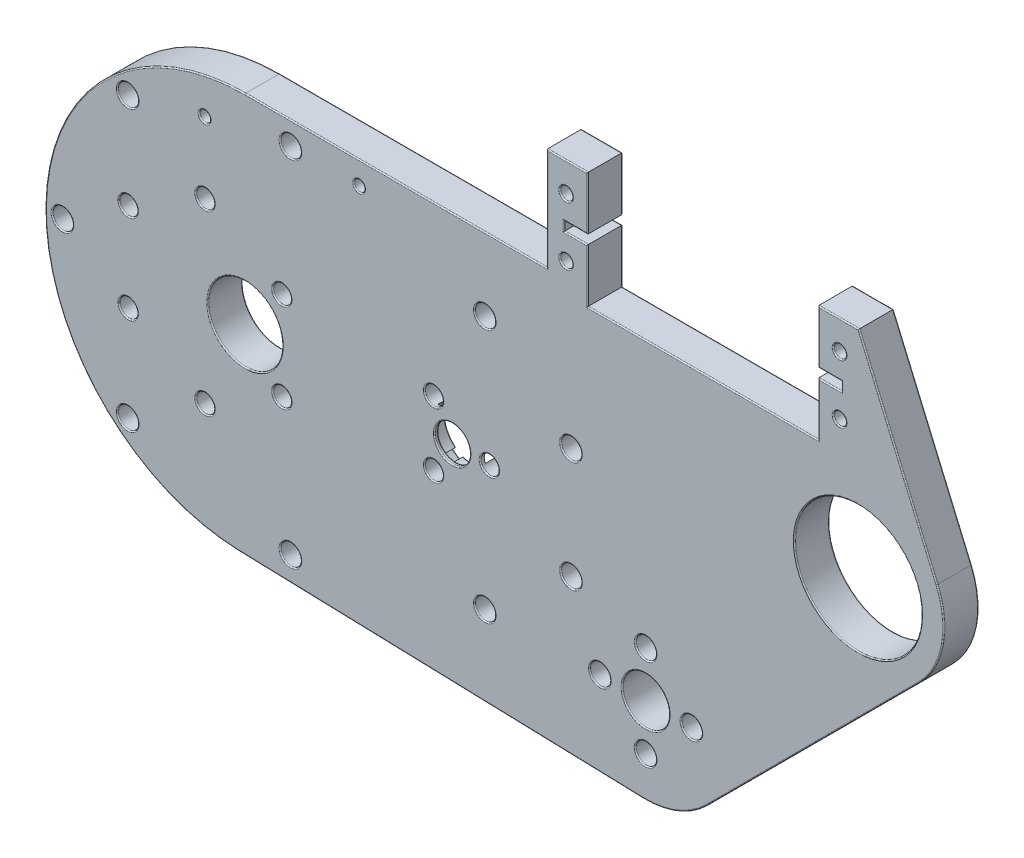
SolidWorks part; units mm, degrees
ref_plane "정면" through (0, 0, 0) normal (0, 0, 1) x (1, 0, 0)
ref_plane "윗면" through (0, 0, 0) normal (0, 1, 0) x (1, 0, 0)
ref_plane "우측면" through (0, 0, 0) normal (1, 0, 0) x (0, 0, -1)
sketch "스케치1" plane through (0, 0, 0) normal (0, 0, 1) x (1, 0, 0)
  line L0 (0, 0) -> (-51.1815, 0) construction
  line L1 (0, 0) -> (0, -16.6153) construction
  line L2 (-29.1144, 27.6051) -> (4.8481, 18.8877)
  line L7 (-29.1144, -27.6051) -> (4.8481, -18.8877)
  line L8 (-29.0149, 27.9926) -> (4.9475, 19.2752)
  line L9 (-29.0149, -27.9926) -> (4.9475, -19.2752)
  line L10 (-27.5232, 33.8042) -> (6.4392, 25.0868)
  line L11 (-27.5232, -33.8042) -> (6.4392, -25.0868)
  circle A3 centre (-43.2, 0) radius 15.5 construction
  circle A4 centre (-36.2, 0) radius 6.5
  circle A5 centre (-43.2, -15.5) radius 1.6
  circle A6 centre (-56.6234, -7.75) radius 1.6
  circle A7 centre (-56.6234, 7.75) radius 1.6
  circle A8 centre (-43.2, 15.5) radius 1.6
  circle A9 centre (-29.7766, 7.75) radius 1.6
  circle A10 centre (-29.7766, -7.75) radius 1.6
  circle A11 centre (0, 0) radius 5.15
  arc A12 (-29.1144, 27.6051) -> (-29.1144, -27.6051) centre (-36.2, 0) ccw
  arc A13 (4.8481, -18.8877) -> (4.8481, 18.8877) centre (0, 0) ccw
  arc A14 (4.9475, -19.2752) -> (4.9475, 19.2752) centre (0, 0) ccw
  arc A15 (-29.0149, 27.9926) -> (-29.0149, -27.9926) centre (-36.2, 0) ccw
  arc A16 (6.4392, -25.0868) -> (6.4392, 25.0868) centre (0, 0) ccw
  arc A17 (-27.5232, 33.8042) -> (-27.5232, -33.8042) centre (-36.2, 0) ccw
  circle A18 centre (0, 0) radius 6.5 construction
  circle A19 centre (6.5, 0) radius 1.6
  circle A20 centre (0, 0) radius 6.5 construction
  circle A21 centre (-3.25, -5.6292) radius 1.6
  circle A22 centre (0, 0) radius 6.5 construction
  circle A23 centre (-3.25, 5.6292) radius 1.6
  point P12 (0, 0)
  point P30 (-43.2, 0)
  point P51 (0, 0)
  dimension "D6" = 31
  dimension "D7" = 13
  dimension "D9" = 3.2
  dimension "D12" = 10.3
  dimension "D13" = 0.4
  dimension "D14" = 57
  dimension "D18" = 39
  dimension "D16" = 13
  dimension "D2" = 3.2
  dimension "D8" = 7
  dimension "D11" = 36.2
  dimension "D15" = 6
  dimension "D10" = 6
  dimension "D3" = 3
extrude "보스-돌출1" add sketch "스케치1" along normal blind 8 contours A23 A11 A21 A19 | L7 A13 L2 A12 A23 A11 A19 A21 A4 A5 A6 A7 A8 A9 A10 | L8 A15 L9 A14 A13 L7 A12 L2 region at (-24.9126, 0, 0) region at (-12.0593, 23.5343, 0) region at (0, 0, 0)
sketch "스케치2" plane through (0, 0, 0) normal (0, 0, -1) x (-1, 0, 0)
  circle A0 centre (0, 0) radius 9
  dimension "D1" = 18
extrude "컷-돌출1" cut sketch "스케치2" against normal blind 3
extrude "보스-돌출2" add sketch "스케치1<3>" along normal blind 29.8 contours L10 A17 L11 A16 A15 L8 A14 L9 region at (-10.8391, 28.288, 0)
sketch "스케치1<3>" plane through (0, 0, 0) normal (0, 0, 1) x (1, 0, 0) same geometry as "스케치1"
sketch "스케치3" plane through (0, 0, 0) normal (0, 0, -1) x (-1, 0, 0)
  line L2 (-33.3521, -36.9933) -> (37.2421, -34.8844)
  line L3 (-71.5915, 30.105) -> (34.6377, 34.865)
  line L4 (-81.5266, 4.5134) -> (-44.4066, -32.6066)
  line L5 (27.5232, 33.8042) -> (-6.4392, 25.0868)
  line L6 (-6.4392, -25.0868) -> (27.5232, -33.8042)
  line L7 (27.5232, 33.8042) -> (-6.4392, 25.0868)
  line L8 (-6.4392, -25.0868) -> (27.5232, -33.8042)
  circle A0 centre (-70.92, 15.12) radius 11.1
  circle A1 centre (-33.8, -22) radius 4.1
  circle A2 centre (36.2, 0) radius 6.5 construction
  arc A3 (-71.5915, 30.105) -> (-81.5266, 4.5134) centre (-70.92, 15.12) ccw
  arc A4 (-44.4066, -32.6066) -> (-33.3521, -36.9933) centre (-33.8, -22) ccw
  arc A5 (27.5232, -33.8042) -> (27.5232, 33.8042) centre (36.2, 0) ccw construction
  arc A7 (-6.4392, 25.0868) -> (-6.4392, -25.0868) centre (0, 0) ccw
  arc A8 (27.5232, -33.8042) -> (27.5232, 33.8042) centre (36.2, 0) ccw
  arc A9 (-6.4392, 25.0868) -> (-6.4392, -25.0868) centre (0, 0) ccw
  arc A10 (27.5232, -33.8042) -> (27.5232, 33.8042) centre (36.2, 0) ccw
  circle A14 centre (-33.8, -14) radius 1.8
  circle A15 centre (-25.8, -22) radius 1.8
  circle A16 centre (-33.8, -30) radius 1.8
  circle A17 centre (-41.8, -22) radius 1.8
  point P32 (-70.92, 15.12)
  point P41 (-33.8, -22)
  line M18 (27.5232, 33.8042) -> (-6.4392, 25.0868)
  arc M19 (-6.4392, 25.0868) -> (-6.4392, -25.0868) centre (0, 0) ccw
  line M20 (-6.4392, -25.0868) -> (27.5232, -33.8042)
  arc M21 (27.5232, -33.8042) -> (27.5232, 33.8042) centre (36.2, 0) ccw
  dimension "D1" = 22.2
  dimension "D2" = 8.2
  dimension "D3" = 70
  dimension "D7" = 30
  dimension "D12" = 3.6
  dimension "D4" = 22
  dimension "D5" = 37.12
  dimension "D6" = 37.12
  dimension "D13" = 8
  dimension "D8" = 0
  dimension "D14" = 4
extrude "보스-돌출3" add sketch "스케치3" against normal blind 5.55 contours L4 A4 L2 L3 A3 A0 A1 M21 M20 M19 M18 region at (36.4383, 0.1602, 0)
sketch "스케치5" plane through (0, 0, 0) normal (0, 0, -1) x (-1, 0, 0)
  line L3 (-33.3521, -36.9933) -> (37.2421, -34.8844)
  line L4 (34.6377, 34.865) -> (-71.5915, 30.105)
  line L5 (-81.5266, 4.5134) -> (-44.4066, -32.6066)
  line L6 (-33.3521, -36.9933) -> (37.2421, -34.8844)
  line L7 (34.6377, 34.865) -> (-71.5915, 30.105)
  line L8 (-81.5266, 4.5134) -> (-44.4066, -32.6066)
  arc A3 (-44.4066, -32.6066) -> (-33.3521, -36.9933) centre (-33.8, -22) ccw
  arc A4 (37.2421, -34.8844) -> (34.6377, 34.865) centre (36.2, 0) ccw
  arc A5 (-71.5915, 30.105) -> (-81.5266, 4.5134) centre (-70.92, 15.12) ccw
  arc A6 (-44.4066, -32.6066) -> (-33.3521, -36.9933) centre (-33.8, -22) ccw
  arc A7 (37.2421, -34.8844) -> (34.6377, 34.865) centre (36.2, 0) ccw
  arc A8 (-71.5915, 30.105) -> (-81.5266, 4.5134) centre (-70.92, 15.12) ccw
  dimension "D1" = 0
extrude "컷-돌출2" cut sketch "스케치5" against normal blind 0.8
sketch "스케치6" plane through (0, 0, 3) normal (0, 0, -1) x (-1, 0, 0)
  circle A0 centre (0, 0) radius 5.15
  dimension "D1" = 10.3
extrude "컷-돌출3" cut sketch "스케치6" against normal blind 3.2 contours A0
sketch "스케치7" plane through (0, 0, 6.2) normal (0, 0, -1) x (-1, 0, 0)
  circle A0 centre (0, 0) radius 3.1
  dimension "D1" = 6.2
extrude "컷-돌출4" cut sketch "스케치7" against normal through all
sketch "스케치8" plane through (0, 0, 8) normal (0, 0, 1) x (1, 0, 0)
  circle A0 centre (-3.25, 5.6292) radius 2.85
  circle A1 centre (6.5, 0) radius 2.85
  circle A2 centre (-3.25, -5.6292) radius 2.85
  dimension "D1" = 5.7
extrude "컷-돌출5" cut sketch "스케치8" against normal blind 1
sketch "스케치9" plane through (0, 0, 29.8) normal (0, 0, 1) x (1, 0, 0)
  line L0 (-29.0149, -27.9926) -> (4.9475, -19.2752) construction
  line L1 (-29.0149, 27.9926) -> (4.9475, 19.2752) construction
  line L2 (6.4392, 25.0868) -> (-27.5232, 33.8042)
  line L3 (-27.5232, -33.8042) -> (6.4392, -25.0868)
  line L4 (6.4392, 25.0868) -> (-27.5232, 33.8042) construction
  line L5 (-27.5232, -33.8042) -> (6.4392, -25.0868) construction
  line L6 (-29.0149, -27.9926) -> (4.9475, -19.2752) construction
  line L7 (-29.0149, 27.9926) -> (4.9475, 19.2752) construction
  line L8 (-28.2691, 30.8984) -> (5.6934, 22.181) construction
  line L9 (-28.2691, -30.8984) -> (5.6934, -22.181) construction
  line L10 (-36.2, 0) -> (-56.7049, 24.4368) construction
  line L11 (-36.2, 0) -> (-68.1, 0) construction
  line L12 (-36.2, 0) -> (-56.7049, -24.4368) construction
  line L13 (0, 0) -> (22.9, 0) construction
  line L14 (0, 0) -> (20.7544, 9.678) construction
  line L15 (0, 0) -> (20.7544, -9.678) construction
  arc A0 (4.9475, -19.2752) -> (4.9475, 19.2752) centre (0, 0) ccw construction
  arc A1 (-29.0149, 27.9926) -> (-29.0149, -27.9926) centre (-36.2, 0) ccw construction
  arc A2 (-27.5232, 33.8042) -> (-27.5232, -33.8042) centre (-36.2, 0) ccw
  arc A3 (6.4392, -25.0868) -> (6.4392, 25.0868) centre (0, 0) ccw
  arc A4 (-27.5232, 33.8042) -> (-27.5232, -33.8042) centre (-36.2, 0) ccw construction
  arc A5 (6.4392, -25.0868) -> (6.4392, 25.0868) centre (0, 0) ccw construction
  arc A6 (4.9475, -19.2752) -> (4.9475, 19.2752) centre (0, 0) ccw construction
  arc A7 (-29.0149, 27.9926) -> (-29.0149, -27.9926) centre (-36.2, 0) ccw construction
  arc A8 (5.6934, -22.181) -> (5.6934, 22.181) centre (0, 0) ccw construction
  arc A9 (-28.2691, 30.8984) -> (-28.2691, -30.8984) centre (-36.2, 0) ccw construction
  circle A10 centre (-28.2691, 30.8984) radius 1.8
  circle A11 centre (5.6934, 22.181) radius 1.8
  circle A12 centre (5.6934, -22.181) radius 1.8
  circle A13 centre (-28.2691, -30.8984) radius 1.8
  circle A14 centre (-56.7049, 24.4368) radius 1.8
  circle A15 centre (-68.1, 0) radius 1.8
  circle A16 centre (-56.7049, -24.4368) radius 1.8
  circle A17 centre (20.7544, 9.678) radius 1.8
  circle A18 centre (20.7544, -9.678) radius 1.8
  dimension "D7" = 3.6
  dimension "D3" = 50
  dimension "D4" = 50
  dimension "D5" = 25
  dimension "D6" = 25
  dimension "D1" = 0
  dimension "D2" = 3
extrude "컷-돌출6" cut sketch "스케치9" against normal through all
sketch "스케치11" plane through (0, 0, 5.55) normal (0, 0, 1) x (1, 0, 0)
  line L5 (44.4066, -32.6066) -> (81.5266, 4.5134)
  line L6 (71.5915, 30.105) -> (-34.6377, 34.865)
  line L7 (-27.5232, 33.8042) -> (6.4392, 25.0868)
  line L8 (6.4392, -25.0868) -> (-27.5232, -33.8042)
  line L9 (-37.2421, -34.8844) -> (33.3521, -36.9933)
  line L10 (44.4066, -32.6066) -> (81.5266, 4.5134)
  line L11 (71.5915, 30.105) -> (-34.6377, 34.865)
  line L12 (-27.5232, 33.8042) -> (6.4392, 25.0868)
  line L13 (6.4392, -25.0868) -> (-27.5232, -33.8042)
  line L14 (-37.2421, -34.8844) -> (33.3521, -36.9933)
  circle A4 centre (70.92, 15.12) radius 11.1 construction
  arc A5 (81.5266, 4.5134) -> (71.5915, 30.105) centre (70.92, 15.12) ccw
  arc A6 (-27.5232, 33.8042) -> (-34.6377, 34.865) centre (-36.2, 0) ccw
  arc A7 (6.4392, -25.0868) -> (6.4392, 25.0868) centre (0, 0) ccw
  arc A8 (-37.2421, -34.8844) -> (-27.5232, -33.8042) centre (-36.2, 0) ccw
  arc A9 (33.3521, -36.9933) -> (44.4066, -32.6066) centre (33.8, -22) ccw
  arc A10 (81.5266, 4.5134) -> (71.5915, 30.105) centre (70.92, 15.12) ccw
  arc A11 (-27.5232, 33.8042) -> (-34.6377, 34.865) centre (-36.2, 0) ccw
  arc A12 (6.4392, -25.0868) -> (6.4392, 25.0868) centre (0, 0) ccw
  arc A13 (-37.2421, -34.8844) -> (-27.5232, -33.8042) centre (-36.2, 0) ccw
  arc A14 (33.3521, -36.9933) -> (44.4066, -32.6066) centre (33.8, -22) ccw
  circle A15 centre (33.8, -30) radius 1.8 construction
  circle A16 centre (41.8, -22) radius 1.8 construction
  circle A17 centre (25.8, -22) radius 1.8 construction
  circle A18 centre (33.8, -22) radius 4.1 construction
  circle A19 centre (33.8, -14) radius 1.8 construction
  circle A24 centre (70.92, 15.12) radius 11.1
  circle A25 centre (33.8, -30) radius 1.8
  circle A26 centre (41.8, -22) radius 1.8
  circle A27 centre (25.8, -22) radius 1.8
  circle A28 centre (33.8, -22) radius 4.1
  circle A29 centre (33.8, -14) radius 1.8
  dimension "D1" = 0
extrude "보스-돌출5" add sketch "스케치11" along normal blind 1.35
sketch "스케치12" plane through (0, 0, 6.9) normal (0, 0, 1) x (1, 0, 0)
  line L1 (-96.1106, 53.9366) -> (93.4119, 53.9366)
  line L2 (-96.1106, 53.9366) -> (-96.1106, -51.4548)
  line L3 (-96.1106, -51.4548) -> (93.4119, -51.4548)
  line L4 (93.4119, 53.9366) -> (93.4119, -51.4548)
extrude "컷-돌출7" cut sketch "스케치12" along normal through all
sketch "스케치15" plane through (0, 0, 0.8) normal (0, 0, -1) x (-1, 0, 0)
  line L0 (-102.7919, 42.7213) -> (70.5846, 42.7213) construction
  line L1 (-43.8, 42.7213) -> (-43.8, 79.9941) construction
  line L2 (-71.05, 52.8713) -> (-16.55, 52.8713)
  line L3 (-71.05, 52.8713) -> (-71.05, 32.5713)
  line L4 (-71.05, 32.5713) -> (-16.55, 32.5713)
  line L5 (-16.55, 52.8713) -> (-16.55, 32.5713)
  line L6 (-71.05, 52.8713) -> (-16.55, 32.5713) construction
  line L7 (-71.05, 32.5713) -> (-16.55, 52.8713) construction
  line L8 (-33.8, -22) -> (-33.8, 95.8728) construction
  line L9 (-63.95, 43.5213) -> (-68.05, 43.5213)
  line L10 (34.6377, 34.865) -> (-71.5915, 30.105) construction
  line L11 (-23.65, 52.8713) -> (-23.65, 32.5713)
  line L12 (-63.95, 52.8713) -> (-63.95, 32.5713)
  line L13 (-16.55, 32.5713) -> (-71.05, 30.1292)
  line L14 (-23.65, 43.5213) -> (-19.55, 43.5213)
  line L15 (-71.05, 32.5713) -> (-71.05, 30.1292)
  line L16 (-68.05, 43.5213) -> (-68.05, 41.9213)
  line L17 (-19.55, 43.5213) -> (-19.55, 41.9213)
  line L18 (-68.05, 41.9213) -> (-63.95, 41.9213)
  line L19 (-19.55, 41.9213) -> (-23.65, 41.9213)
  line L20 (34.6377, 34.865) -> (-71.5915, 30.105)
  line L21 (-71.05, 52.8713) -> (-84.7055, 21.0326)
  line L22 (36.2, 34.9) -> (-16.55, 34.9)
  circle A0 centre (-67.7, 47.8213) radius 2.05
  circle A1 centre (-19.9, 47.8213) radius 2.05
  circle A2 centre (-19.9, 37.6213) radius 2.05
  circle A3 centre (-67.7, 37.6213) radius 2.05
  circle A4 centre (-67.7, 47.8213) radius 1.1
  circle A5 centre (-67.7, 37.6213) radius 1.1
  circle A6 centre (-19.9, 47.8213) radius 1.1
  circle A7 centre (-19.9, 37.6213) radius 1.1
  arc A8 (37.2421, -34.8844) -> (34.6377, 34.865) centre (36.2, 0) ccw construction
  arc A9 (-71.5915, 30.105) -> (-81.5266, 4.5134) centre (-70.92, 15.12) ccw construction
  arc A10 (36.2, 34.9) -> (34.6377, 34.865) centre (36.2, 0) ccw
  arc A11 (-71.5915, 30.105) -> (-84.7055, 21.0326) centre (-70.92, 15.12) ccw
  point P2 (-43.8, 42.7213)
  point P29 (-33.8, 42.7213)
  point P47 (0, 0)
  arc M37 (37.2421, -34.8844) -> (34.6377, 34.865) centre (36.2, 0) ccw
  line M38 (34.6377, 34.865) -> (-71.5915, 30.105)
  arc M39 (-71.5915, 30.105) -> (-81.5266, 4.5134) centre (-70.92, 15.12) ccw
  dimension "D7" = 4.1
  dimension "D5" = 2.2
  dimension "D1" = 54.5
  dimension "D2" = 20.3
  dimension "D3" = 5.1
  dimension "D4" = 23.9
  dimension "D6" = 40.3
  dimension "D8" = 17.25
  dimension "D9" = 3
  dimension "D10" = 1.6
  dimension "D11" = 0.8
extrude "보스-돌출6" add sketch "스케치15" against normal up to surface (6.1 mm away) contours L12 L2 L3 L4 A0 A3 | L4 L15 M38 | L2 L11 L4 L5 A2 A1 | A0 A4 | A3 A5 | A1 A6 | A2 A7 | L3 L21 L15 M39 M38 | L22 L5 M37 M38 region at (67.5, 52.6563, 0.8) region at (75.0044, 36.4285, 0.8) region at (52.8833, 31.7573, 0.8) region at (20.1, 52.6563, 0.8) region at (-0.7754, 34.1238, 0.8) region at (69.692, 47.8213, 0.8) region at (21.892, 47.8213, 0.8) region at (21.892, 37.6213, 0.8) region at (69.692, 37.6213, 0.8) up to face at (22.1098, -5.2653, 6.9)
sketch "스케치16" plane through (0, 0, 6.9) normal (0, 0, 1) x (1, 0, 0)
  line L0 (-46.7691, 27.8984) -> (-46.7691, 38.4984)
  line L1 (-46.7691, 38.4984) -> (-12.7691, 38.4984)
  line L2 (-12.7691, 38.4984) -> (-12.7691, 30.8984)
  line L3 (-46.7691, 35.4984) -> (-12.7691, 35.4984)
  line L4 (-40.9881, 25.2437) -> (-30.8758, 33.9323)
  line L5 (-25.7691, 34.0209) -> (-18.4566, 28.1662)
  circle A0 centre (-28.2691, 30.8984) radius 4
  circle A1 centre (-16.2691, 30.8984) radius 0.95
  circle A2 centre (-16.2691, 30.8984) radius 3.5
  circle A3 centre (-43.2691, 27.8984) radius 3.5
  circle A4 centre (-43.2691, 27.8984) radius 0.95
  point P17 (-26.7164, 34.7793)
  dimension "D1" = 8
  dimension "D2" = 1.9
  dimension "D3" = 7
  dimension "D7" = 7
  dimension "D8" = 1.9
  dimension "D4" = 12
  dimension "D5" = 3
  dimension "D6" = 15
  dimension "D9" = 3
  dimension "D10" = 10.6
extrude "컷-돌출8" cut sketch "스케치16" against normal through all contours A4 | A1 region at (-16.2691, 30.8984, 6.9) region at (-43.2691, 27.8984, 6.9)
fillet "필렛1" radius 0.2 111 edges at (21, 47.8213, 6.9) (68.8, 37.6213, 6.9) (21, 37.6213, 6.9) (68.8, 47.8213, 6.9) (-26.4691, 30.8984, 6.9) (22.5544, 9.678, 6.9) (22.5544, -9.678, 6.9) (-54.9049, -24.4368, 6.9) (-66.3, 0, 6.9) (-54.9049, 24.4368, 6.9) (-26.4691, -30.8984, 6.9) (7.4934, -22.181, 6.9) (7.4934, 22.181, 6.9) (-29.7, 0, 6.9) (-41.6, -15.5, 6.9) (-55.0234, -7.75, 6.9) (-55.0234, 7.75, 6.9) (-41.6, 15.5, 6.9) (-28.1766, 7.75, 6.9) (-28.1766, -7.75, 6.9) (-1.65, -5.6292, 6.9) (8.1, 0, 6.9) (-1.65, 5.6292, 6.9) (35.6, -14, 6.9) (27.6, -22, 6.9) (35.6, -30, 6.9) (82.02, 15.12, 6.9) (43.6, -22, 6.9) (37.9, -22, 6.9) (62.9666, -14.0466, 6.9) (39.3327, -35.9424, 6.9) (-1.945, -35.9389, 6.9) (-71.0961, 0.5211, 6.9) (-9.825, 34.9, 6.9) (16.55, 43.8857, 6.9) (20.1, 52.8713, 6.9) (23.65, 48.1963, 6.9) (21.6, 43.5213, 6.9) (19.55, 42.7213, 6.9) (21.6, 41.9213, 6.9) (23.65, 37.2463, 6.9) (43.8, 32.5713, 6.9) (63.95, 37.2463, 6.9) (66, 41.9213, 6.9) (68.05, 42.7213, 6.9) (66, 43.5213, 6.9) (63.95, 48.1963, 6.9) (67.5, 52.8713, 6.9) (77.8778, 36.952, 6.9) (85.6497, 12.2854, 6.9) (-15.3191, 30.8984, 6.9) (-42.3191, 27.8984, 6.9) (3.1, 0, 6.9) (-3.1, 0, 6.2) (-9, 0, 3) (8.1, 0, 3) (2.575, -4.46, 3) (-4.05, -7.0148, 3) (-5.15, 0, 3) (-4.05, 7.0148, 3) (2.575, 4.46, 3) (18.8, 37.6213, 0.8) (18.8, 47.8213, 0.8) (66.6, 47.8213, 0.8) (66.6, 37.6213, 0.8) (-9, 0, 0.8) (29.7, -22, 0.8) (59.82, 15.12, 0.8) (32, -14, 0.8) (24, -22, 0.8) (32, -30, 0.8) (40, -22, 0.8) (-42.7, 0, 0.8) (-44.8, -15.5, 0.8) (-58.2234, -7.75, 0.8) (-58.2234, 7.75, 0.8) (-44.8, 15.5, 0.8) (-31.3766, 7.75, 0.8) (-31.3766, -7.75, 0.8) (7.4934, 22.181, 0.8) (7.4934, -22.181, 0.8) (-26.4691, -30.8984, 0.8) (-54.9049, 24.4368, 0.8) (-66.3, 0, 0.8) (-54.9049, -24.4368, 0.8) (22.5544, -9.678, 0.8) (22.5544, 9.678, 0.8) (-26.4691, 30.8984, 0.8) (67.5, 52.8713, 0.8) (63.95, 48.1963, 0.8) (66, 43.5213, 0.8) (68.05, 42.7213, 0.8) (66, 41.9213, 0.8) (63.95, 37.2463, 0.8) (43.8, 32.5713, 0.8) (23.65, 37.2463, 0.8) (21.6, 41.9213, 0.8) (19.55, 42.7213, 0.8) (21.6, 43.5213, 0.8) (23.65, 48.1963, 0.8) (20.1, 52.8713, 0.8) (16.55, 43.8857, 0.8) (-9.825, 34.9, 0.8) (-71.0961, 0.5211, 0.8) (-1.945, -35.9389, 0.8) (39.3327, -35.9424, 0.8) (62.9666, -14.0466, 0.8) (85.6497, 12.2854, 0.8) (77.8778, 36.952, 0.8) (-15.3191, 30.8984, 0.8) (-42.3191, 27.8984, 0.8)
